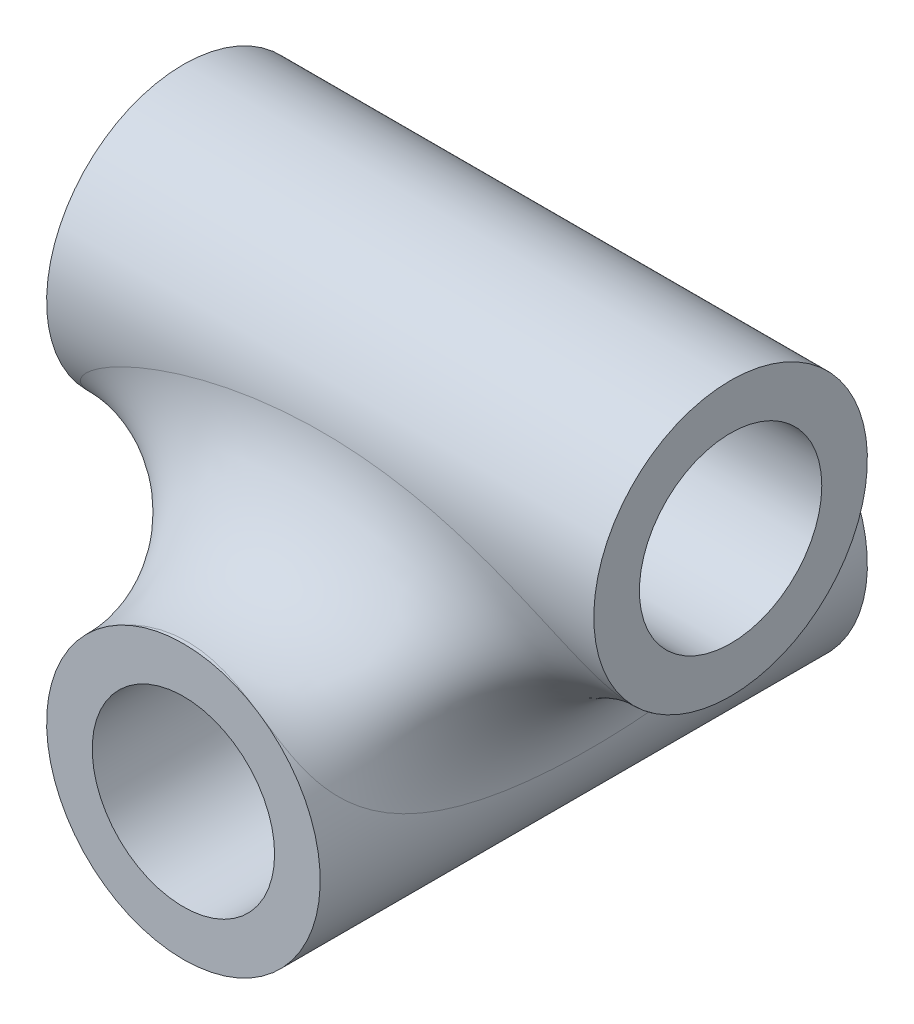
SolidWorks part; units mm, degrees
material "ABS"
ref_plane "Front Plane" through (0, 0, 0) normal (0, 0, 1) x (1, 0, 0)
ref_plane "Top Plane" through (0, 0, 0) normal (0, 1, 0) x (1, 0, 0)
ref_plane "Right Plane" through (0, 0, 0) normal (1, 0, 0) x (0, 0, -1)
sketch "Sketch1" plane through (0, 0, 0) normal (0, 0, 1) x (1, 0, 0)
  circle A0 centre (0, 0) radius 10
  circle A1 centre (0, 0) radius 15
  dimension "D1" = 20
  dimension "D2" = 30
extrude "Boss-Extrude1" add sketch "Sketch1" along normal blind 30 and the other way blind 30
sketch "Sketch2" plane through (0, 0, 0) normal (1, 0, 0) x (0, 0, -1)
  line L0 (0, 16.5) -> (0, -16.5) construction
  line L4 (-30, 10) -> (30, 10) construction
  circle A0 centre (0, 25) radius 10
  circle A1 centre (0, 25) radius 15
  dimension "D1" = 20
  dimension "D3" = 30
extrude "Boss-Extrude2" add sketch "Sketch2" along normal blind 30 and the other way blind 30
fillet "Fillet1" radius 15 1 edges at (1.4038, 14.9342, 11.1211)
